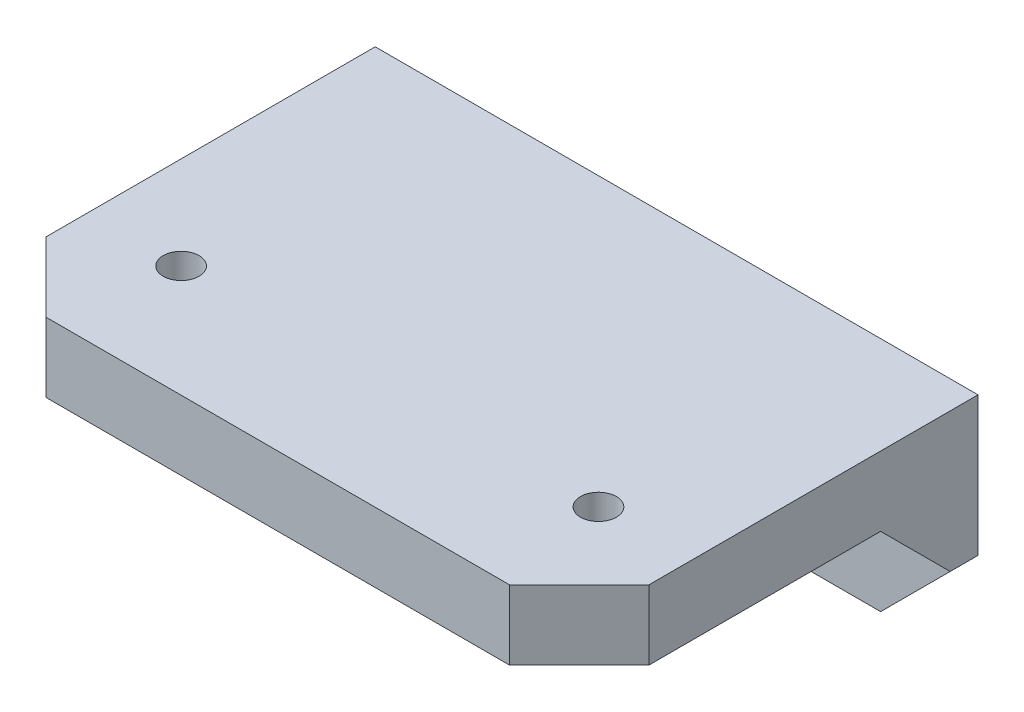
SolidWorks part; units mm, degrees
material "PET"
ref_plane "Front Plane" through (0, 0, 0) normal (0, 0, 1) x (1, 0, 0)
ref_plane "Top Plane" through (0, 0, 0) normal (0, 1, 0) x (1, 0, 0)
ref_plane "Right Plane" through (0, 0, 0) normal (1, 0, 0) x (0, 0, -1)
sketch "Sketch1" plane through (0, 0, 0) normal (0, 0, 1) x (1, 0, 0)
  line L1 (-151.095, -53.975) -> (-126.4888, -53.975)
  line L2 (-209.0388, -25.4) -> (-126.4888, -25.4)
  line L3 (-209.0388, -25.4) -> (-209.0388, -53.975)
  line L4 (-209.0388, -53.975) -> (-151.095, -53.975)
  line L5 (-126.4888, -25.4) -> (-126.4888, -53.975)
  point P0 (-151.7052, -53.975)
extrude "Boss-Extrude1" add sketch "Sketch1" along normal blind 6.35
sketch "Sketch2" plane through (0, 0, 6.35) normal (0, 0, 1) x (1, 0, 0)
  line L0 (-126.4888, -53.975) -> (-126.4888, -25.4) construction
  line L1 (-209.0388, -25.4) -> (-126.4888, -25.4)
  line L2 (-209.0388, -25.4) -> (-209.0388, -34.925)
  line L3 (-209.0388, -34.925) -> (-126.4888, -34.925)
  line L4 (-126.4888, -25.4) -> (-126.4888, -34.925)
  dimension "D1" = 9.525
extrude "Boss-Extrude2" add sketch "Sketch2" along normal blind 50.8
chamfer "Chamfer1" distance 9.525 angle 45 5 edges at (-167.7638, -34.925, 6.35) (-126.4888, -53.975, 3.175) (-126.4888, -30.1625, 57.15) (-209.0388, -30.1625, 57.15) (-209.0388, -53.975, 3.175)
hole_wizard "#8 Clearance Hole1" positions "Sketch3" profile "Sketch4" hole size "#8" standard "ANSI Inch" end condition through all
sketch "Sketch3" plane through (0, 0, 57.15) normal (0, 0, 1) x (1, 0, 0)
  line L0 (-126.4888, -44.45) -> (-209.0388, -44.45) construction
  line L1 (-209.0388, -44.45) -> (-209.0388, -34.925) construction
  line L2 (-126.4888, -34.925) -> (-126.4888, -44.45) construction
  point P0 (-193.1638, -44.45)
  point P2 (-142.3638, -44.45)
  point P5 (-149.7734, -40.08)
  point P8 (0, 0)
  dimension "D1" = 15.875
  dimension "D2" = 15.875
sketch "Sketch4" plane through (-193.1638, -44.45, 57.15) normal (1, 0, 0) x (0, -1, 0)
  line L0 (0, 0) -> (0, 57.15)
  line L1 (0, 57.15) -> (2.4574, 57.15)
  line L2 (2.4574, 57.15) -> (2.4574, 0)
  line L5 (2.4574, 0) -> (0, 0)
  line L11 (0, -6.35) -> (0, 107.95) construction
  dimension "Thru Hole Dia." = 4.9149
  dimension "Thru Hole Depth" = 57.15
sketch "Sketch5" plane through (0, 0, 6.35) normal (0, 0, 1) x (1, 0, 0)
  circle A0 centre (-193.1638, -44.45) radius 6.35
  circle A1 centre (-142.3638, -44.45) radius 6.35
  dimension "D1" = 12.7
extrude "Cut-Extrude1" cut sketch "Sketch5" along normal up to next
hole_wizard "#8 Clearance Hole2" positions "Sketch6" profile "Sketch7" hole size "#8" standard "ANSI Inch" end condition through all
sketch "Sketch6" plane through (0, -34.925, 0) normal (0, -1, 0) x (-1, 0, 0)
  line L0 (209.0388, -47.625) -> (209.0388, -15.875) construction
  line L1 (126.4888, -47.625) -> (126.4888, -15.875) construction
  point P0 (196.3388, -41.8183)
  point P2 (139.1888, -41.8183)
  point P5 (0, 0)
  dimension "D1" = 12.7
  dimension "D2" = 12.7
sketch "Sketch7" plane through (-196.3388, -34.925, 41.8183) normal (1, 0, 0) x (0, 0, -1)
  line L0 (0, 0) -> (0, 9.525)
  line L1 (0, 9.525) -> (2.4574, 9.525)
  line L2 (2.4574, 9.525) -> (2.4574, 0)
  line L5 (2.4574, 0) -> (0, 0)
  line L11 (0, -6.35) -> (0, 107.95) construction
  dimension "Thru Hole Dia." = 4.9149
  dimension "Thru Hole Depth" = 9.525
chamfer "Chamfer2" distance 2.54 angle 45 6 edges at (-167.7638, -25.4, 0) (-126.4888, -34.925, 0) (-131.2513, -49.2125, 0) (-167.7638, -53.975, 0) (-204.2763, -49.2125, 0) (-209.0388, -34.925, 0)
ref_plane "Plane4" through (-167.7638, 0, 0) normal (1, 0, 0) x (0, 0, -1)
